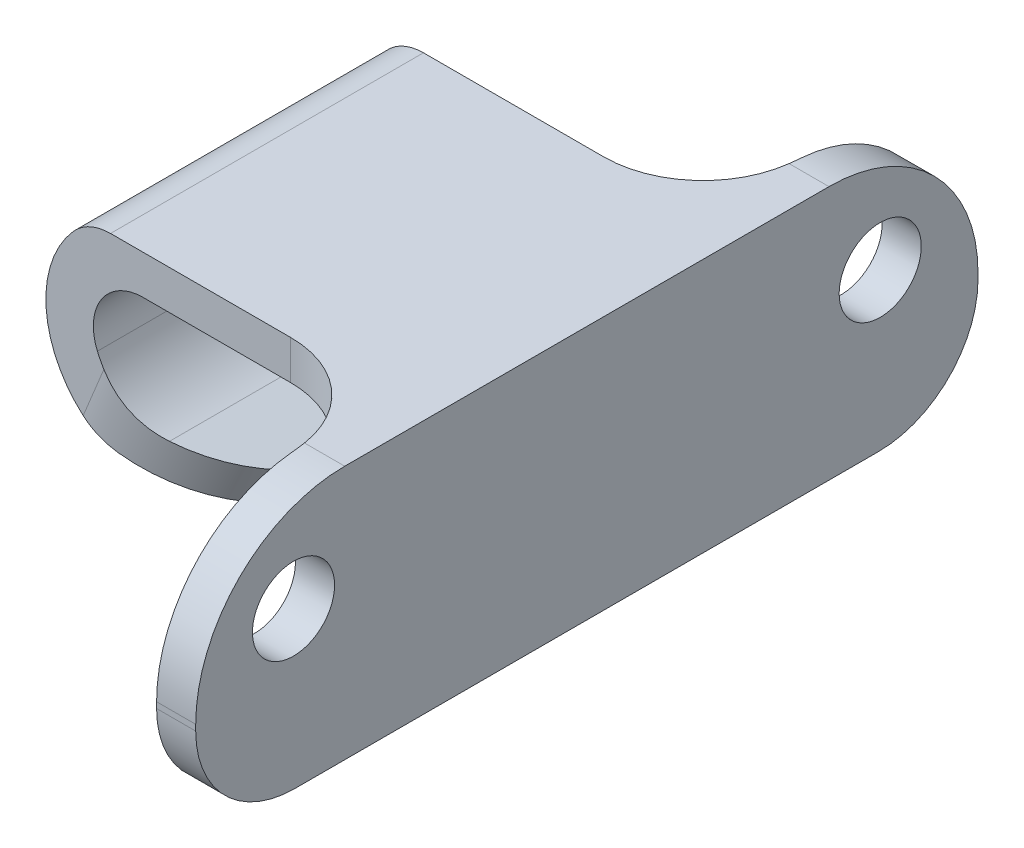
SolidWorks part; units mm, degrees
material "AISI 304"
ref_plane "Front Plane" through (0, 0, 0) normal (0, 0, 1) x (1, 0, 0)
ref_plane "Top Plane" through (0, 0, 0) normal (0, 1, 0) x (1, 0, 0)
ref_plane "Right Plane" through (0, 0, 0) normal (1, 0, 0) x (0, 0, -1)
sketch "Sketch1" plane through (0, 0, 0) normal (1, 0, 0) x (0, 0, -1)
  line L0 (0, 6.5) -> (0, -6.5) construction
  line L1 (-20, 6.5) -> (20, 6.5)
  line L2 (-20, 6.5) -> (-20, -6.5)
  line L3 (-20, -6.5) -> (20, -6.5)
  line L4 (20, 6.5) -> (20, -6.5)
  circle A0 centre (-15, 1.5) radius 2.1
  circle A1 centre (15, 1.5) radius 2.1
  dimension "D4" = 4.2
  dimension "D1" = 39.9999
  dimension "D2" = 5
  dimension "D3" = 29.9999
  dimension "D5" = 13
extrude "Boss-Extrude1" add sketch "Sketch1" along normal blind 2
fillet "Fillet1" radius 7.62 2 edges at (1, 6.5, -20) (1, 6.5, 20)
fillet "Fillet2" radius 5.08 2 edges at (1, -6.5, -20) (1, -6.5, 20)
sketch "Sketch2" plane through (0, 6.5, 0) normal (0, 1, 0) x (1, 0, 0)
  line L1 (-15.24, 7.939) -> (0, 7.939)
  line L2 (-15.24, 7.939) -> (-15.24, -8.061)
  line L3 (-15.24, -8.061) -> (0, -8.061)
  line L4 (0, 7.939) -> (0, -8.061)
  line L7 (0, 12.38) -> (0, -12.38) construction
  line L8 (0, -12.38) -> (2, -12.38) construction
  point P4 (0, -0.061)
  point P9 (0, -0.061)
  dimension "D1" = 16
  dimension "D2" = 15.24
  dimension "D3" = 12.319
extrude "Boss-Extrude2" add sketch "Sketch2" against normal blind 2
fillet "Fillet3" radius 5.08 2 edges at (0, 5.5, -7.939) (0, 5.5, 8.061)
sketch "Sketch3" plane through (0, 0, 8.061) normal (0, 0, 1) x (1, 0, 0)
  line L1 (0, -6.2704) -> (0, -4.3735)
  line L3 (-12.0204, -1.9381) -> (-7.9985, -3.5887)
  line L4 (-7.9985, -3.5887) -> (-8.7574, -5.438)
  line L5 (-8.7574, -5.438) -> (-14.1342, -3.2314)
  line L7 (-14.769, 6.5) -> (-18.8629, 6.5)
  line L8 (-15.24, 6.5) -> (-5.08, 6.5) construction
  arc A1 (-14.1342, -3.2314) -> (-12.0204, -1.9381) centre (-15.0178, 0.587) ccw
  arc A2 (-14.1342, -3.2314) -> (-15.24, 6.5) centre (-12.0127, 1.9382) cw
  arc A3 (-12.0204, -1.9381) -> (-15.24, 4.5) centre (-9.9424, 3.1251) cw
  line M8 (-15.24, 4.5) -> (-5.08, 4.5)
  dimension "D3" = 7.8386
  dimension "D5" = 5.588
  dimension "D1" = 7.9985
  dimension "D2" = 11.938
  dimension "D4" = 1.999
extrude "Boss-Extrude3" add sketch "Sketch3" against normal up to surface (16 mm away) contours A1 L5 L4 L3 | A1 L5 M8
fillet "Fillet4" radius 7.62 2 edges at (-8.3779, -4.5133, -7.939) (-8.3779, -4.5133, 8.061)
fillet "Fillet5" radius 2.54 2 edges at (-15.24, 4.5, 0.061) (-15.24, 6.5, 0.061)
fillet "Fillet6" radius 2.032 1 edges at (0, 4.5, 0.061)
